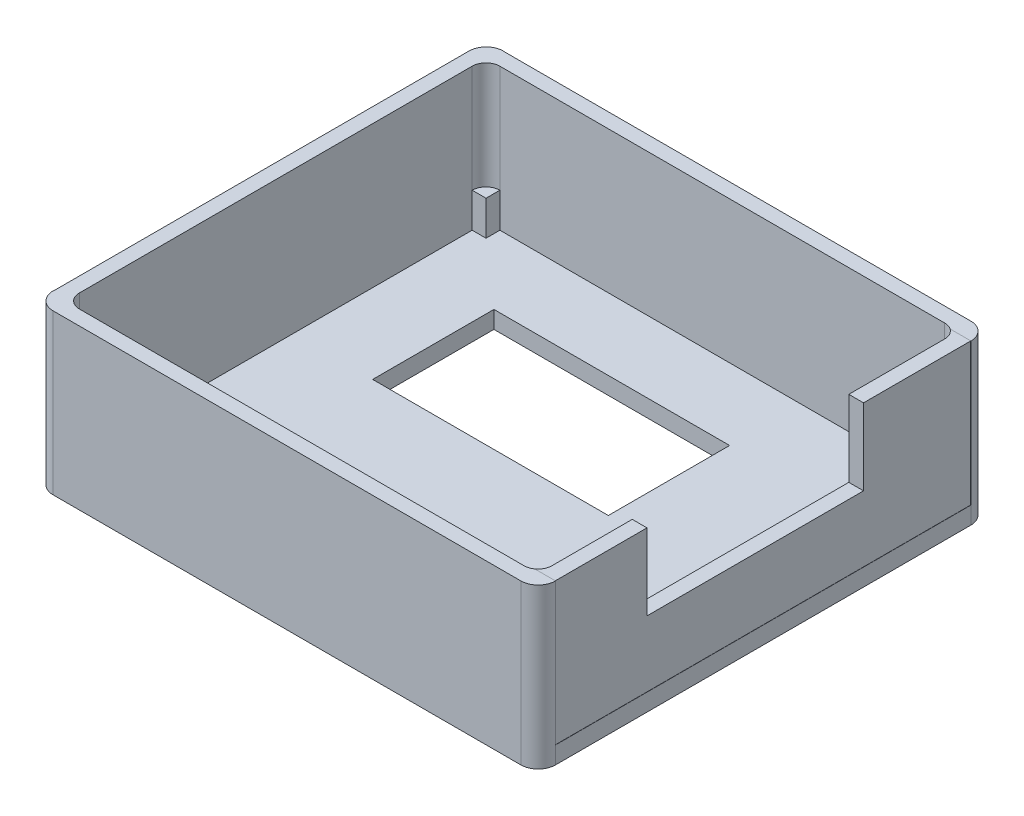
SolidWorks part; units mm, degrees
ref_plane "前视基准面" through (0, 0, 0) normal (0, 0, 1) x (1, 0, 0)
ref_plane "上视基准面" through (0, 0, 0) normal (0, 1, 0) x (1, 0, 0)
ref_plane "右视基准面" through (0, 0, 0) normal (1, 0, 0) x (0, 0, -1)
sketch "草图1" plane through (0, 0, 0) normal (0, 0, 1) x (1, 0, 0)
  line L0 (-0.873, -1.6001) -> (-25.8731, -1.6001) construction
  line L1 (-25.8731, -1.6001) -> (-27.8731, -1.6001) construction
  line L2 (-27.8731, -1.6001) -> (-27.8731, 0) construction
  line L3 (-27.8731, 0) -> (-0.873, 0) construction
  line L4 (-0.873, 0) -> (1.127, 0) construction
  line L5 (1.127, 0) -> (1.127, -1.6001) construction
  line L6 (1.127, -1.6001) -> (-0.873, -1.6001) construction
  line L7 (-27.8731, 0) -> (-27.8731, 4.5999) construction
  line L8 (-27.8731, 4.5999) -> (1.127, 4.5999) construction
  line L9 (1.127, 4.5999) -> (1.127, -1.6001) construction
  line L10 (1.127, -1.6001) -> (1.127, -3.6001) construction
  line L11 (1.127, -3.6001) -> (-27.8731, -3.6001) construction
  line L12 (-27.8731, -3.6001) -> (-27.8731, -1.6001) construction
  line L14 (-27.8731, 4.5999) -> (1.127, 4.5999)
  line L15 (-27.8731, 4.5999) -> (-27.8731, -3.6001)
  line L16 (-27.8731, -3.6001) -> (1.127, -3.6001)
  line L17 (1.127, 4.5999) -> (1.127, -3.6001)
extrude "凸台-拉伸1" add sketch "草图1" along normal blind 1
sketch "草图3" plane through (-26.8604, 0, 0) normal (-1, 0, 0) x (0, 0, 1)
  line L0 (0, -3.6001) -> (-22.9873, -3.6001) construction
  line L1 (-22.9873, -3.6001) -> (-22.9873, -1.6001) construction
  line L2 (-22.9873, -1.6001) -> (-24.9873, -1.6001) construction
  line L3 (-24.9873, -1.6001) -> (-24.9873, -3.6001) construction
  line L4 (-24.9873, -3.6001) -> (-22.9873, -3.6001) construction
  line L5 (-24.9873, -1.6001) -> (-24.9873, 0) construction
  line L6 (-24.9873, 0) -> (-24.9873, 4.5999) construction
  line L7 (-24.9873, 4.5999) -> (-0.9873, 4.5999) construction
  line L8 (-0.9873, 4.5999) -> (0.0127, 4.5999) construction
  line L10 (0, -3.6001) -> (-24.9873, -3.6001)
  line L11 (0, -3.6001) -> (0, 4.5999)
  line L12 (0, 4.5999) -> (-24.9873, 4.5999)
  line L13 (-24.9873, -3.6001) -> (-24.9873, 4.5999)
extrude "凸台-拉伸2" add sketch "草图3" along normal blind 1
sketch "草图4" plane through (0, 0, -23.9746) normal (0, 0, -1) x (-1, 0, 0)
  line L0 (26.8604, 4.5999) -> (-1.127, 4.5999) construction
  line L1 (-1.127, 4.5999) -> (-1.127, -3.6001) construction
  line L2 (27.8604, -3.6001) -> (26.8604, -3.6001) construction
  line L3 (-1.127, 4.5999) -> (26.8604, 4.5999)
  line L4 (-1.127, 4.5999) -> (-1.127, -3.6001)
  line L5 (-1.127, -3.6001) -> (26.8604, -3.6001)
  line L6 (26.8604, 4.5999) -> (26.8604, -3.6001)
  line L7 (26.8604, 4.5999) -> (26.8604, -3.6001) construction
extrude "凸台-拉伸3" add sketch "草图4" along normal blind 1
sketch "草图6" plane through (0.1143, 0, 0) normal (1, 0, 0) x (0, 0, -1)
  line L0 (22.9873, 0) -> (23.9836, 0) construction
  line L1 (23.9836, 0) -> (23.9836, 4.6) construction
  line L2 (23.9836, 4.6) -> (0, 4.6) construction
  line L3 (0, 4.6) -> (0, -3.6) construction
  line L5 (0, -3.6) -> (23.9836, -3.6)
  line L6 (0, -3.6) -> (0, 4.6)
  line L7 (0, 4.6) -> (23.9836, 4.6)
  line L8 (23.9836, -3.6) -> (23.9836, 4.6)
extrude "凸台-拉伸4" add sketch "草图6" along normal blind 1
sketch "草图9" plane through (1.1143, 0, 0) normal (1, 0, 0) x (0, 0, -1)
  line L0 (17.7912, 4.6) -> (17.7912, 0.2) construction
  line L1 (23.9836, 4.6) -> (0, 4.6) construction
  line L2 (17.7912, 0.1) -> (17.7912, 3.9) construction
  line L3 (17.7912, 4.6) -> (5.2912, 4.6) construction
  line L4 (5.2912, 3.9) -> (5.2912, 0.1) construction
  line L6 (5.2912, 4.6) -> (17.7912, 4.6)
  line L7 (5.2912, 4.6) -> (5.2912, 0.2)
  line L8 (5.2912, 0.2) -> (17.7912, 0.2)
  line L9 (17.7912, 4.6) -> (17.7912, 0.2)
extrude "切除-拉伸1" cut sketch "草图9" against normal blind 1
sketch "草图10" plane through (0, -3.6, 0) normal (0, -1, 0) x (1, 0, 0)
  line L1 (1.127, -24.9746) -> (-27.8731, -24.9746)
  line L2 (1.127, -24.9746) -> (1.127, 1)
  line L3 (1.127, 1) -> (-27.8731, 1)
  line L4 (-27.8731, -24.9746) -> (-27.8731, 1)
extrude "凸台-拉伸5" add sketch "草图10" along normal blind 1
sketch "草图11" plane through (0, -4.6, 0) normal (0, -1, 0) x (1, 0, 0)
  line L0 (-12.319, -16.4943) -> (-12.319, -19.9943) construction
  line L1 (-12.319, -19.9943) -> (-8.819, -19.9943) construction
  line L2 (-18.923, -16.4943) -> (-18.923, -12.9943) construction
  line L3 (-18.923, -12.9943) -> (-22.423, -12.9943) construction
  line L5 (-8.819, -19.9943) -> (-22.423, -19.9943)
  line L6 (-8.819, -19.9943) -> (-8.819, -12.9943)
  line L7 (-8.819, -12.9943) -> (-22.423, -12.9943)
  line L8 (-22.423, -19.9943) -> (-22.423, -12.9943)
extrude "切除-拉伸3" cut sketch "草图11" against normal blind 1 contours L7 L8 L5 L6
fillet "圆角1" radius 1 4 edges at (1.127, 0, -24.9746) (1.127, 0, 1) (-27.8731, 0, 1) (-27.8731, -4.1, -24.9746)
fillet "圆角2" radius 1 1 edges at (-27.8604, 0.4999, -24.9873)
sketch "草图12" plane through (0, 4.6, 0) normal (0, 1, 0) x (1, 0, 0)
  line L0 (-26.8604, 23.9746) -> (-27.0104, 23.9746) construction
  line L1 (-27.0104, 23.9746) -> (-27.0104, 24.1246) construction
  line L2 (0.1143, 0) -> (0.2643, 0) construction
  line L3 (1.1143, 0) -> (0.1143, 0) construction
  line L4 (0.2643, 0) -> (0.2643, -0.15) construction
  line L6 (0.2643, -0.15) -> (-27.0104, -0.15)
  line L7 (0.2643, -0.15) -> (0.2643, 24.1246)
  line L8 (0.2643, 24.1246) -> (-27.0104, 24.1246)
  line L9 (-27.0104, -0.15) -> (-27.0104, 24.1246)
  line L10 (-26.8604, 23.9746) -> (0.1143, 23.9746)
  line L11 (-26.8604, 23.9746) -> (-26.8604, 0)
  line L12 (-26.8604, 0) -> (0.1143, 0)
  line L13 (0.1143, 23.9746) -> (0.1143, 0)
extrude "切除-拉伸4" cut sketch "草图12" against normal up to surface (8.2 mm away) up to face at (-15.621, -3.6, -16.4943)
sketch "草图14" plane through (0, -3.6, 0) normal (0, 1, 0) x (1, 0, 0)
  line L1 (-27.0104, 24.1246) -> (-26.2104, 24.1246)
  line L2 (-27.0104, 24.1246) -> (-27.0104, 23.3246)
  line L3 (-27.0104, 23.3246) -> (-26.2104, 23.3246)
  line L4 (-26.2104, 24.1246) -> (-26.2104, 23.3246)
  line L5 (0.2643, -0.15) -> (-0.5357, -0.15)
  line L6 (0.2643, -0.15) -> (0.2643, 0.65)
  line L7 (0.2643, 0.65) -> (-0.5357, 0.65)
  line L8 (-0.5357, -0.15) -> (-0.5357, 0.65)
extrude "凸台-拉伸6" add sketch "草图14" along normal up to surface (1.9999 mm away)
fillet "圆角3" radius 0.8 4 edges at (-27.0104, 0.5, 0.15) (0.2643, 1.4999, 0.15) (0.2643, 0.5, -24.1246) (-27.0104, 1.4999, -24.1246)
